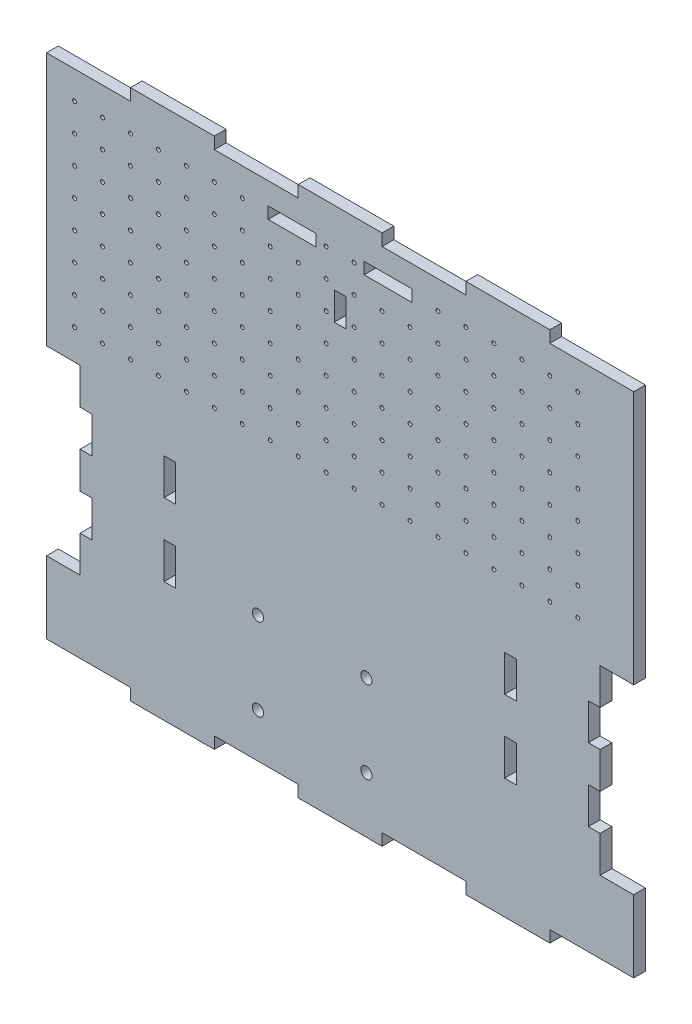
SolidWorks part; units mm, degrees
ref_plane "Front Plane" through (0, 0, 0) normal (0, 0, 1) x (1, 0, 0)
ref_plane "Top Plane" through (0, 0, 0) normal (0, 1, 0) x (1, 0, 0)
ref_plane "Right Plane" through (0, 0, 0) normal (1, 0, 0) x (0, 0, -1)
sketch "Sketch1" plane through (0, 0, 0) normal (0, 0, 1) x (1, 0, 0)
  line L1 (-133.35, 120.65) -> (133.35, 120.65)
  line L2 (-133.35, 120.65) -> (-133.35, -120.65)
  line L3 (-133.35, -120.65) -> (133.35, -120.65)
  line L4 (133.35, 120.65) -> (133.35, -120.65)
  line L5 (-133.35, 120.65) -> (133.35, -120.65) construction
  line L6 (-133.35, -120.65) -> (133.35, 120.65) construction
  point P0 (0, 0)
  dimension "D1" = 241.3
  dimension "D2" = 266.7
extrude "Boss-Extrude1" add sketch "Sketch1" along normal blind 5.334
sketch "Sketch2" plane through (0, 0, 0) normal (0, 0, -1) x (-1, 0, 0)
  line L0 (133.35, 120.65) -> (133.35, -120.65) construction
  line L1 (133.35, 0) -> (118.11, 0)
  line L2 (133.35, 0) -> (133.35, -82.55)
  line L3 (133.35, -82.55) -> (118.11, -82.55)
  line L4 (118.11, 0) -> (118.11, -82.55)
  line L5 (-133.35, -120.65) -> (-133.35, 120.65) construction
  line L6 (-133.35, 0) -> (-118.11, 0)
  line L7 (-133.35, 0) -> (-133.35, -82.55)
  line L8 (-133.35, -82.55) -> (-118.11, -82.55)
  line L9 (-118.11, 0) -> (-118.11, -82.55)
  line L10 (133.35, -120.65) -> (-133.35, -120.65) construction
  dimension "D1" = 82.55
  dimension "D2" = 82.55
  dimension "D3" = 38.1
  dimension "D4" = 38.1
  dimension "D5" = 15.24
  dimension "D6" = 15.24
extrude "Cut-Extrude1" cut sketch "Sketch2" against normal through all
sketch "Sketch9" plane through (0, 0, 5.334) normal (0, 0, 1) x (1, 0, 0)
  line L0 (-118.11, 0) -> (-118.11, -82.55) construction
  line L1 (-118.11, -16.51) -> (-112.776, -16.51)
  line L2 (-118.11, -16.51) -> (-118.11, -33.02)
  line L3 (-118.11, -33.02) -> (-112.776, -33.02)
  line L4 (-112.776, -16.51) -> (-112.776, -33.02)
  line L5 (-118.11, 0) -> (-112.776, 0) construction
  line L6 (-118.11, -49.53) -> (-112.776, -49.53)
  line L7 (-118.11, -49.53) -> (-118.11, -66.04)
  line L8 (-118.11, -66.04) -> (-112.776, -66.04)
  line L9 (-112.776, -49.53) -> (-112.776, -66.04)
  line L10 (-112.776, 0) -> (-112.776, -16.51) construction
  line L11 (-112.776, -33.02) -> (-112.776, -49.53) construction
  line L12 (-118.11, -82.55) -> (-112.776, -82.55) construction
  line L13 (-112.776, -82.55) -> (-112.776, -66.04) construction
  line L14 (0, -120.65) -> (0, 120.65) construction
  line L15 (-133.35, -120.65) -> (133.35, -120.65) construction
  line L16 (133.35, 120.65) -> (-133.35, 120.65) construction
  line L17 (112.776, -82.55) -> (112.776, -66.04) construction
  line L18 (118.11, -82.55) -> (112.776, -82.55) construction
  line L19 (112.776, -33.02) -> (112.776, -49.53) construction
  line L20 (112.776, 0) -> (112.776, -16.51) construction
  line L21 (118.11, 0) -> (112.776, 0) construction
  line L22 (112.776, -49.53) -> (112.776, -66.04)
  line L23 (118.11, -66.04) -> (112.776, -66.04)
  line L24 (118.11, -49.53) -> (118.11, -66.04)
  line L25 (118.11, -49.53) -> (112.776, -49.53)
  line L26 (112.776, -16.51) -> (112.776, -33.02)
  line L27 (118.11, -33.02) -> (112.776, -33.02)
  line L28 (118.11, -16.51) -> (118.11, -33.02)
  line L29 (118.11, -16.51) -> (112.776, -16.51)
  dimension "D1" = 5.334
extrude "Cut-Extrude2" cut sketch "Sketch9" against normal through all
sketch "Sketch10" plane through (0, 0, 5.334) normal (0, 0, 1) x (1, 0, 0)
  line L2 (-133.35, -120.65) -> (133.35, -120.65) construction
  line L3 (-133.35, -82.55) -> (-133.35, -120.65) construction
  circle A0 centre (-37.338, -95.25) radius 2.54
  circle A1 centre (11.938, -95.25) radius 2.54
  circle A2 centre (11.938, -57.912) radius 2.54
  circle A3 centre (-37.338, -57.912) radius 2.54
  dimension "D1" = 96.012
  dimension "D2" = 49.276
  dimension "D3" = 25.4
  dimension "D4" = 2
  dimension "D5" = 2
extrude "Cut-Extrude3" cut sketch "Sketch10" against normal through all
sketch "Sketch19" plane through (0, 0, 5.334) normal (0, 0, 1) x (1, 0, 0)
  line L0 (-10.8958, 100.076) -> (10.8958, 100.076) construction
  line L1 (-32.6875, 105.41) -> (-10.8958, 105.41)
  line L2 (-32.6875, 105.41) -> (-32.6875, 100.076)
  line L3 (-32.6875, 100.076) -> (-10.8958, 100.076)
  line L4 (-10.8958, 105.41) -> (-10.8958, 100.076)
  line L5 (10.8958, 105.41) -> (32.6875, 105.41)
  line L6 (10.8958, 105.41) -> (10.8958, 100.076)
  line L7 (10.8958, 100.076) -> (32.6875, 100.076)
  line L8 (32.6875, 105.41) -> (32.6875, 100.076)
  line L9 (-32.6875, 100.076) -> (-133.35, 100.076) construction
  line L10 (-133.35, 120.65) -> (-133.35, 0) construction
  line L11 (32.6875, 100.076) -> (133.35, 100.076) construction
  line L12 (133.35, 0) -> (133.35, 120.65) construction
  line L13 (133.35, 120.65) -> (-133.35, 120.65) construction
  dimension "D1" = 15.24
  dimension "D2" = 5.334
  dimension "D3" = 5.334
  dimension "D4" = 21.7917
sketch "Sketch23" plane through (0, 0, 5.334) normal (0, 0, 1) x (1, 0, 0)
  line L0 (-112.776, -24.765) -> (-61.976, -24.765) construction
  line L1 (-112.776, -33.02) -> (-112.776, -16.51) construction
  line L2 (-112.776, -16.51) -> (-74.676, -16.51) construction
  line L3 (-112.776, -33.02) -> (-74.676, -33.02) construction
  line L4 (-118.11, -41.275) -> (118.11, -41.275) construction
  line L5 (-118.11, -33.02) -> (-118.11, -49.53) construction
  line L6 (118.11, -49.53) -> (118.11, -33.02) construction
  line L7 (-112.776, -49.53) -> (-74.676, -49.53) construction
  line L8 (-112.776, -57.785) -> (-61.976, -57.785) construction
  line L9 (-112.776, -66.04) -> (-74.676, -66.04) construction
  line L10 (0, -120.65) -> (0, 120.65) construction
  line L11 (-133.35, -120.65) -> (133.35, -120.65) construction
  line L12 (133.35, 120.65) -> (-133.35, 120.65) construction
  line L13 (112.776, -66.04) -> (74.676, -66.04) construction
  line L14 (112.776, -49.53) -> (74.676, -49.53) construction
  line L15 (112.776, -33.02) -> (74.676, -33.02) construction
  line L16 (112.776, -16.51) -> (74.676, -16.51) construction
  line L17 (-74.676, -66.04) -> (-80.01, -66.04)
  line L18 (74.676, -16.51) -> (80.01, -16.51)
  line L19 (74.676, -16.51) -> (74.676, -33.02)
  line L20 (74.676, -33.02) -> (80.01, -33.02)
  line L21 (80.01, -16.51) -> (80.01, -33.02)
  line L22 (74.676, -49.53) -> (80.01, -49.53)
  line L23 (74.676, -49.53) -> (74.676, -66.04)
  line L24 (74.676, -66.04) -> (80.01, -66.04)
  line L25 (80.01, -49.53) -> (80.01, -66.04)
  line L26 (-80.01, -49.53) -> (-80.01, -66.04)
  line L27 (-74.676, -49.53) -> (-74.676, -66.04)
  line L28 (-74.676, -49.53) -> (-80.01, -49.53)
  line L29 (-74.676, -33.02) -> (-80.01, -33.02)
  line L30 (-80.01, -16.51) -> (-80.01, -33.02)
  line L31 (-74.676, -16.51) -> (-80.01, -16.51)
  line L32 (-74.676, -16.51) -> (-74.676, -33.02)
  line L33 (112.776, -16.51) -> (112.776, -33.02) construction
  dimension "D1" = 5.334
  dimension "D2" = 5.334
  dimension "D3" = 32.766
  dimension "D4" = 32.766
extrude "Cut-Extrude8" cut sketch "Sketch23" against normal through all
extrude "Cut-Extrude9" cut sketch "Sketch19" against normal through all contours L1 L4 L3 L2
sketch "Sketch24" plane through (0, 0, 0) normal (0, 0, -1) x (-1, 0, 0)
  line L0 (0, 120.65) -> (0, -120.65) construction
  line L1 (-133.35, 120.65) -> (133.35, 120.65) construction
  line L2 (133.35, -120.65) -> (-133.35, -120.65) construction
extrude "Cut-Extrude11" cut sketch "Sketch19<5>" against normal through all
sketch "Sketch19<5>" plane through (0, 0, 5.334) normal (0, 0, 1) x (1, 0, 0) same geometry as "Sketch19"
sketch "Sketch26" plane through (0, 0, 5.334) normal (0, 0, 1) x (1, 0, 0)
sketch "Sketch27" plane through (0, 0, 5.334) normal (0, 0, 1) x (1, 0, 0)
  line L0 (10.8958, 100.076) -> (32.6875, 100.076) construction
  line L1 (-2.667, 87.376) -> (2.667, 87.376)
  line L2 (-2.667, 87.376) -> (-2.667, 74.676)
  line L3 (-2.667, 74.676) -> (2.667, 74.676)
  line L4 (2.667, 87.376) -> (2.667, 74.676)
  line L9 (133.35, 0) -> (133.35, 120.65) construction
  line L10 (-133.35, 120.65) -> (-133.35, 0) construction
  line L11 (2.667, 74.676) -> (133.35, 74.676) construction
  line L12 (-2.667, 74.676) -> (-133.35, 74.676) construction
  dimension "D1" = 12.7
  dimension "D4" = 12.7
  dimension "D5" = 5.334
extrude "Cut-Extrude12" cut sketch "Sketch27" against normal through all
sketch "Sketch28" plane through (0, 0, 0) normal (0, 0, -1) x (-1, 0, 0)
  line L0 (133.35, -120.65) -> (-133.35, -120.65) construction
  line L1 (-133.35, -120.65) -> (-95.25, -120.65)
  line L2 (-133.35, -120.65) -> (-133.35, -115.316)
  line L3 (-133.35, -115.316) -> (-95.25, -115.316)
  line L4 (-95.25, -120.65) -> (-95.25, -115.316)
  line L5 (-57.15, -120.65) -> (-19.05, -120.65)
  line L6 (-57.15, -120.65) -> (-57.15, -115.316)
  line L7 (-57.15, -115.316) -> (-19.05, -115.316)
  line L8 (-19.05, -120.65) -> (-19.05, -115.316)
  line L9 (133.35, -82.55) -> (133.35, -120.65) construction
  line L10 (19.05, -120.65) -> (57.15, -120.65)
  line L11 (19.05, -120.65) -> (19.05, -115.316)
  line L12 (19.05, -115.316) -> (57.15, -115.316)
  line L13 (57.15, -120.65) -> (57.15, -115.316)
  line L14 (95.25, -120.65) -> (133.35, -120.65)
  line L16 (95.25, -115.316) -> (133.35, -115.316)
  line L17 (133.35, -120.65) -> (133.35, -115.316)
  line L18 (-95.25, -115.316) -> (-57.15, -115.316) construction
  line L19 (-19.05, -115.316) -> (19.05, -115.316) construction
  line L20 (95.25, -115.316) -> (57.15, -115.316) construction
  line L21 (133.35, 120.65) -> (133.35, -115.316) construction
  line L22 (133.35, -115.316) -> (133.5431, -115.1744) construction
  line L41 (95.25, -120.65) -> (95.25, -115.316)
  dimension "D1" = 5.334
extrude "Cut-Extrude13" cut sketch "Sketch28" against normal through all
sketch "Sketch29" plane through (0, 0, 0) normal (0, 0, -1) x (-1, 0, 0)
  line L0 (-133.35, 120.65) -> (133.35, 120.65) construction
  line L1 (-133.35, 120.65) -> (-95.25, 120.65)
  line L2 (-133.35, 120.65) -> (-133.35, 115.316)
  line L3 (-133.35, 115.316) -> (-95.25, 115.316)
  line L4 (-95.25, 120.65) -> (-95.25, 115.316)
  line L5 (-57.15, 120.65) -> (-19.05, 120.65)
  line L6 (-57.15, 120.65) -> (-57.15, 115.316)
  line L7 (-57.15, 115.316) -> (-19.05, 115.316)
  line L8 (-19.05, 120.65) -> (-19.05, 115.316)
  line L9 (133.35, 120.65) -> (133.35, 0) construction
  line L10 (19.05, 120.65) -> (57.15, 120.65)
  line L11 (19.05, 120.65) -> (19.05, 115.316)
  line L12 (19.05, 115.316) -> (57.15, 115.316)
  line L13 (57.15, 120.65) -> (57.15, 115.316)
  line L14 (95.25, 120.65) -> (133.35, 120.65)
  line L15 (95.25, 120.65) -> (95.25, 115.316)
  line L16 (95.25, 115.316) -> (133.35, 115.316)
  line L17 (133.35, 120.65) -> (133.35, 115.316)
  line L18 (-95.25, 115.316) -> (-57.15, 115.316) construction
  line L19 (19.05, 115.316) -> (-19.05, 115.316) construction
  line L20 (57.15, 115.316) -> (95.25, 115.316) construction
  dimension "D1" = 5.334
extrude "Cut-Extrude14" cut sketch "Sketch29" against normal through all
sketch "Sketch30" plane through (0, 0, 5.334) normal (0, 0, 1) x (1, 0, 0)
  line L0 (-95.25, 115.316) -> (-133.35, 115.316) construction
  line L1 (-133.35, 115.316) -> (-133.35, 0) construction
  line L2 (-120.65, 102.616) -> (-107.95, 102.616) construction
  circle A0 centre (-120.65, 102.616) radius 0.889
  circle A1 centre (-107.95, 102.616) radius 0.889
  circle A2 centre (-95.25, 102.616) radius 0.889
  circle A3 centre (-82.55, 102.616) radius 0.889
  circle A4 centre (-69.85, 102.616) radius 0.889
  circle A5 centre (-57.15, 102.616) radius 0.889
  circle A6 centre (-44.45, 102.616) radius 0.889
  circle A7 centre (-31.75, 102.616) radius 0.889 [skipped]
  circle A8 centre (-19.05, 102.616) radius 0.889 [skipped]
  circle A9 centre (-6.35, 102.616) radius 0.889
  circle A10 centre (6.35, 102.616) radius 0.889
  circle A11 centre (19.05, 102.616) radius 0.889 [skipped]
  circle A12 centre (31.75, 102.616) radius 0.889 [skipped]
  circle A13 centre (44.45, 102.616) radius 0.889
  circle A14 centre (57.15, 102.616) radius 0.889
  circle A15 centre (69.85, 102.616) radius 0.889
  circle A16 centre (82.55, 102.616) radius 0.889
  circle A17 centre (95.25, 102.616) radius 0.889
  circle A18 centre (107.95, 102.616) radius 0.889
  circle A19 centre (-107.95, 89.916) radius 0.889
  circle A20 centre (-95.25, 89.916) radius 0.889
  circle A21 centre (-82.55, 89.916) radius 0.889
  circle A22 centre (-69.85, 89.916) radius 0.889
  circle A23 centre (-57.15, 89.916) radius 0.889
  circle A24 centre (-44.45, 89.916) radius 0.889
  circle A25 centre (-31.75, 89.916) radius 0.889
  circle A26 centre (-19.05, 89.916) radius 0.889
  circle A27 centre (-6.35, 89.916) radius 0.889
  circle A28 centre (6.35, 89.916) radius 0.889
  circle A29 centre (19.05, 89.916) radius 0.889
  circle A30 centre (31.75, 89.916) radius 0.889
  circle A31 centre (44.45, 89.916) radius 0.889
  circle A32 centre (57.15, 89.916) radius 0.889
  circle A33 centre (69.85, 89.916) radius 0.889
  circle A34 centre (82.55, 89.916) radius 0.889
  circle A35 centre (95.25, 89.916) radius 0.889
  circle A36 centre (107.95, 89.916) radius 0.889
  circle A37 centre (-107.95, 77.216) radius 0.889
  circle A38 centre (-95.25, 77.216) radius 0.889
  circle A39 centre (-82.55, 77.216) radius 0.889
  circle A40 centre (-69.85, 77.216) radius 0.889
  circle A41 centre (-57.15, 77.216) radius 0.889
  circle A42 centre (-44.45, 77.216) radius 0.889
  circle A43 centre (-31.75, 77.216) radius 0.889
  circle A44 centre (-19.05, 77.216) radius 0.889
  circle A45 centre (-6.35, 77.216) radius 0.889
  circle A46 centre (6.35, 77.216) radius 0.889
  circle A47 centre (19.05, 77.216) radius 0.889
  circle A48 centre (31.75, 77.216) radius 0.889
  circle A49 centre (44.45, 77.216) radius 0.889
  circle A50 centre (57.15, 77.216) radius 0.889
  circle A51 centre (69.85, 77.216) radius 0.889
  circle A52 centre (82.55, 77.216) radius 0.889
  circle A53 centre (95.25, 77.216) radius 0.889
  circle A54 centre (107.95, 77.216) radius 0.889
  circle A55 centre (-107.95, 64.516) radius 0.889
  circle A56 centre (-95.25, 64.516) radius 0.889
  circle A57 centre (-82.55, 64.516) radius 0.889
  circle A58 centre (-69.85, 64.516) radius 0.889
  circle A59 centre (-57.15, 64.516) radius 0.889
  circle A60 centre (-44.45, 64.516) radius 0.889
  circle A61 centre (-31.75, 64.516) radius 0.889
  circle A62 centre (-19.05, 64.516) radius 0.889
  circle A63 centre (-6.35, 64.516) radius 0.889
  circle A64 centre (6.35, 64.516) radius 0.889
  circle A65 centre (19.05, 64.516) radius 0.889
  circle A66 centre (31.75, 64.516) radius 0.889
  circle A67 centre (44.45, 64.516) radius 0.889
  circle A68 centre (57.15, 64.516) radius 0.889
  circle A69 centre (69.85, 64.516) radius 0.889
  circle A70 centre (82.55, 64.516) radius 0.889
  circle A71 centre (95.25, 64.516) radius 0.889
  circle A72 centre (107.95, 64.516) radius 0.889
  circle A73 centre (-107.95, 51.816) radius 0.889
  circle A74 centre (-95.25, 51.816) radius 0.889
  circle A75 centre (-82.55, 51.816) radius 0.889
  circle A76 centre (-69.85, 51.816) radius 0.889
  circle A77 centre (-57.15, 51.816) radius 0.889
  circle A78 centre (-44.45, 51.816) radius 0.889
  circle A79 centre (-31.75, 51.816) radius 0.889
  circle A80 centre (-19.05, 51.816) radius 0.889
  circle A81 centre (-6.35, 51.816) radius 0.889
  circle A82 centre (6.35, 51.816) radius 0.889
  circle A83 centre (19.05, 51.816) radius 0.889
  circle A84 centre (31.75, 51.816) radius 0.889
  circle A85 centre (44.45, 51.816) radius 0.889
  circle A86 centre (57.15, 51.816) radius 0.889
  circle A87 centre (69.85, 51.816) radius 0.889
  circle A88 centre (82.55, 51.816) radius 0.889
  circle A89 centre (95.25, 51.816) radius 0.889
  circle A90 centre (107.95, 51.816) radius 0.889
  circle A91 centre (-107.95, 39.116) radius 0.889
  circle A92 centre (-95.25, 39.116) radius 0.889
  circle A93 centre (-82.55, 39.116) radius 0.889
  circle A94 centre (-69.85, 39.116) radius 0.889
  circle A95 centre (-57.15, 39.116) radius 0.889
  circle A96 centre (-44.45, 39.116) radius 0.889
  circle A97 centre (-31.75, 39.116) radius 0.889
  circle A98 centre (-19.05, 39.116) radius 0.889
  circle A99 centre (-6.35, 39.116) radius 0.889
  circle A100 centre (6.35, 39.116) radius 0.889
  circle A101 centre (19.05, 39.116) radius 0.889
  circle A102 centre (31.75, 39.116) radius 0.889
  circle A103 centre (44.45, 39.116) radius 0.889
  circle A104 centre (57.15, 39.116) radius 0.889
  circle A105 centre (69.85, 39.116) radius 0.889
  circle A106 centre (82.55, 39.116) radius 0.889
  circle A107 centre (95.25, 39.116) radius 0.889
  circle A108 centre (107.95, 39.116) radius 0.889
  circle A109 centre (-107.95, 26.416) radius 0.889
  circle A110 centre (-95.25, 26.416) radius 0.889
  circle A111 centre (-82.55, 26.416) radius 0.889
  circle A112 centre (-69.85, 26.416) radius 0.889
  circle A113 centre (-57.15, 26.416) radius 0.889
  circle A114 centre (-44.45, 26.416) radius 0.889
  circle A115 centre (-31.75, 26.416) radius 0.889
  circle A116 centre (-19.05, 26.416) radius 0.889
  circle A117 centre (-6.35, 26.416) radius 0.889
  circle A118 centre (6.35, 26.416) radius 0.889
  circle A119 centre (19.05, 26.416) radius 0.889
  circle A120 centre (31.75, 26.416) radius 0.889
  circle A121 centre (44.45, 26.416) radius 0.889
  circle A122 centre (57.15, 26.416) radius 0.889
  circle A123 centre (69.85, 26.416) radius 0.889
  circle A124 centre (82.55, 26.416) radius 0.889
  circle A125 centre (95.25, 26.416) radius 0.889
  circle A126 centre (107.95, 26.416) radius 0.889
  circle A127 centre (-107.95, 13.716) radius 0.889
  circle A128 centre (-95.25, 13.716) radius 0.889
  circle A129 centre (-82.55, 13.716) radius 0.889
  circle A130 centre (-69.85, 13.716) radius 0.889
  circle A131 centre (-57.15, 13.716) radius 0.889
  circle A132 centre (-44.45, 13.716) radius 0.889
  circle A133 centre (-31.75, 13.716) radius 0.889
  circle A134 centre (-19.05, 13.716) radius 0.889
  circle A135 centre (-6.35, 13.716) radius 0.889
  circle A136 centre (6.35, 13.716) radius 0.889
  circle A137 centre (19.05, 13.716) radius 0.889
  circle A138 centre (31.75, 13.716) radius 0.889
  circle A139 centre (44.45, 13.716) radius 0.889
  circle A140 centre (57.15, 13.716) radius 0.889
  circle A141 centre (69.85, 13.716) radius 0.889
  circle A142 centre (82.55, 13.716) radius 0.889
  circle A143 centre (95.25, 13.716) radius 0.889
  circle A144 centre (107.95, 13.716) radius 0.889
  circle A145 centre (-120.65, 89.916) radius 0.889
  circle A146 centre (-120.65, 77.216) radius 0.889
  circle A147 centre (-120.65, 64.516) radius 0.889
  circle A148 centre (-120.65, 51.816) radius 0.889
  circle A149 centre (-120.65, 39.116) radius 0.889
  circle A150 centre (-120.65, 26.416) radius 0.889
  circle A151 centre (-120.65, 13.716) radius 0.889
  dimension "D1" = 1.778
  dimension "D2" = 12.7
  dimension "D3" = 12.7
  dimension "D6" = 12.7
  dimension "D4" = 19
  dimension "D5" = 8
extrude "Cut-Extrude15" cut sketch "Sketch30" against normal through all
equation "\"MDF\"= .21in"
equation "\"Foamcore\"= .13in"
equation "\"Gmaterial\"= \"MDF\""
equation "\"D1@Sketch9\"=\"MDF\""
equation "\"D2@Sketch19\"=\"MDF\""
equation "\"D3@Sketch19\"=\"MDF\""
equation "\"D1@Sketch23\"=\"MDF\""
equation "\"D2@Sketch23\"=\"D1@Sketch23\""
equation "\"D1@Boss-Extrude1\"=\"MDF\""
equation "\"D3@Sketch23\"=1.29"
equation "\"D5@Sketch27\"=\"MDF\""
equation "\"D1@Sketch28\"=\"MDF\""
equation "\"D1@Sketch29\"=\"MDF\""
